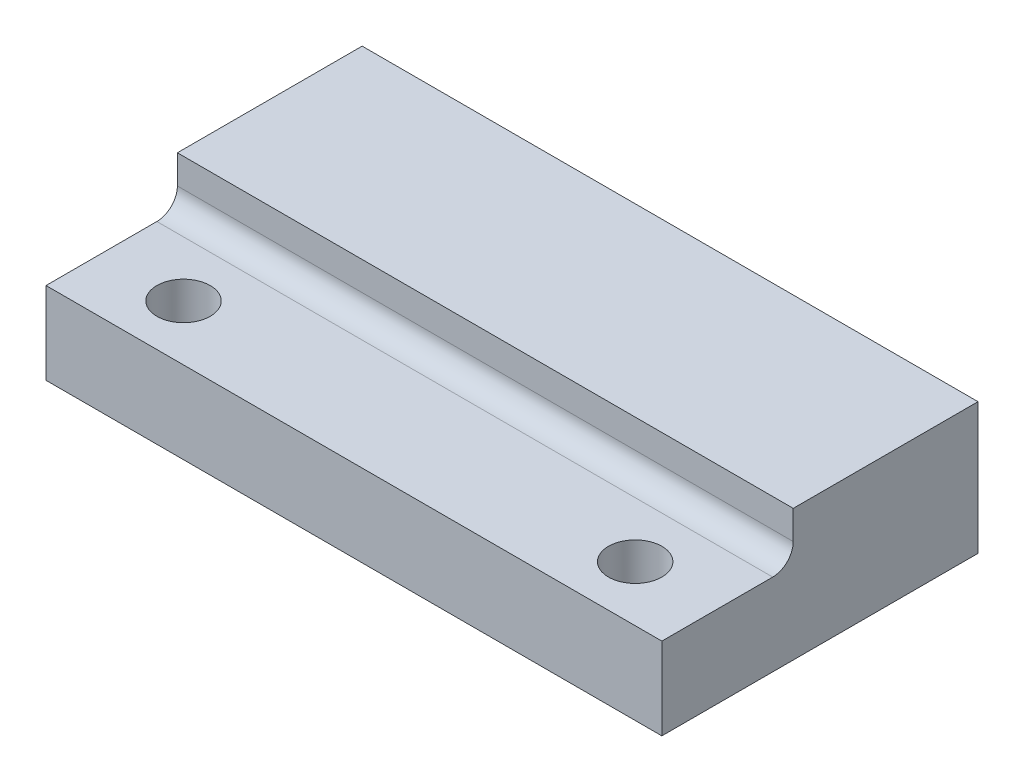
SolidWorks part; units mm, degrees
material "Stainless Steel (ferritic)"
ref_plane "Front Plane" through (0, 0, 0) normal (0, 0, 1) x (1, 0, 0)
ref_plane "Top Plane" through (0, 0, 0) normal (0, 1, 0) x (1, 0, 0)
ref_plane "Right Plane" through (0, 0, 0) normal (1, 0, 0) x (0, 0, -1)
sketch "Sketch1" plane through (0, 0, 0) normal (0, 1, 0) x (1, 0, 0)
  line L1 (-30, 15.4) -> (0, 15.4)
  line L2 (-30, 15.4) -> (-30, 0)
  line L3 (-30, 0) -> (0, 0)
  line L4 (0, 15.4) -> (0, 0)
  point P0 (-30, 0)
  dimension "D1" = 15.4
  dimension "D2" = 30
extrude "Boss-Extrude1" add sketch "Sketch1" along normal blind 6.4
sketch "Sketch4" plane through (0, 0, 0) normal (0, 1, 0) x (1, 0, 0)
  line L1 (0, 0) -> (0, 15.4) construction
  line L2 (-30, 0) -> (0, 0) construction
  circle A0 centre (-26, 2.7) radius 1.3
  circle A1 centre (-4, 2.7) radius 1.3
  dimension "D2" = 4
  dimension "D3" = 2.7
  dimension "D4" = 2.6
  dimension "D1" = 22
extrude "Cut-Extrude3" cut sketch "Sketch4" along normal through all
sketch "Sketch8" plane through (0, 0, 0) normal (1, 0, 0) x (0, 0, -1)
  line L0 (0, 0) -> (15.4, 0) construction
  line L1 (0, 6.4) -> (11.4, 6.4)
  line L2 (0, 6.4) -> (0, 4)
  line L3 (0, 4) -> (11.4, 4)
  line L4 (11.4, 6.4) -> (11.4, 4)
  line L5 (15.4, 6.4) -> (15.4, 0) construction
  dimension "D1" = 4
  dimension "D2" = 4
extrude "Cut-Extrude4" cut sketch "Sketch8" against normal through all
sketch "Sketch9" plane through (0, 0, -15.4) normal (0, 0, -1) x (-1, 0, 0)
  line L0 (0, 6.4) -> (0, 0) construction
  line L1 (0, 0) -> (30, 0) construction
  circle A0 centre (4, 3.7) radius 0.5
  circle A1 centre (26, 3.7) radius 0.5
  dimension "D1" = 4
  dimension "D2" = 22
  dimension "D3" = 3.7
  dimension "D4" = 1
extrude "Cut-Extrude5" cut sketch "Sketch9" against normal blind 7
hole_wizard "M2x0.4 Tapped Hole1" positions "Sketch10" profile "Sketch12" tap size "M2x0.4" standard "ANSI Metric"
sketch "Sketch10" plane through (0, 0, -15.4) normal (0, 0, -1) x (-1, 0, 0)
  point P0 (4, 3.7)
  point P3 (26, 3.7)
sketch "Sketch12" plane through (-4, 3.7, -15.4) normal (1, 0, 0) x (0, 1, 0)
  line L0 (0, 0) -> (0, 7.4807)
  line L1 (0, 7.4807) -> (0.8, 7)
  line L2 (0.8, 7) -> (0.8, 0)
  line L5 (0.8, 0) -> (0, 0)
  line L10 (0, 7.4807) -> (-0.8, 7) construction
  line L11 (0, -6.35) -> (0, 107.95) construction
  dimension "Tap Drill Dia." = 1.6
  dimension "Tap Drill Depth" = 7
  dimension "Drill Angle" = 118
cosmetic thread "Hole Thread1" parameters "D1"=4, "D2"=2
cosmetic thread "Hole Thread2" parameters "D1"=4, "D2"=2
sketch "Sketch14" plane through (0, 6.4, 0) normal (0, 1, 0) x (1, 0, 0)
  line L0 (0, 0) -> (0, 11.4) construction
  line L1 (-30, 11.4) -> (0, 11.4)
  line L2 (-30, 11.4) -> (-30, 6.4)
  line L3 (-30, 6.4) -> (0, 6.4)
  line L4 (0, 11.4) -> (0, 6.4)
  dimension "D1" = 5
extrude "Boss-Extrude2" add sketch "Sketch14" against normal up to surface (2.4 mm away) up to face at (-26, 4, -4)
sketch "Sketch13" plane through (0, 0, -15.4) normal (0, 0, -1) x (-1, 0, 0)
  circle A0 centre (4, 3.7) radius 1
  circle A1 centre (26, 3.7) radius 1
  dimension "D1" = 2
extrude "Cut-Extrude6" cut sketch "Sketch13" against normal blind 7
fillet "Fillet1" radius 1 1 edges at (-15, 4, -6.4)
